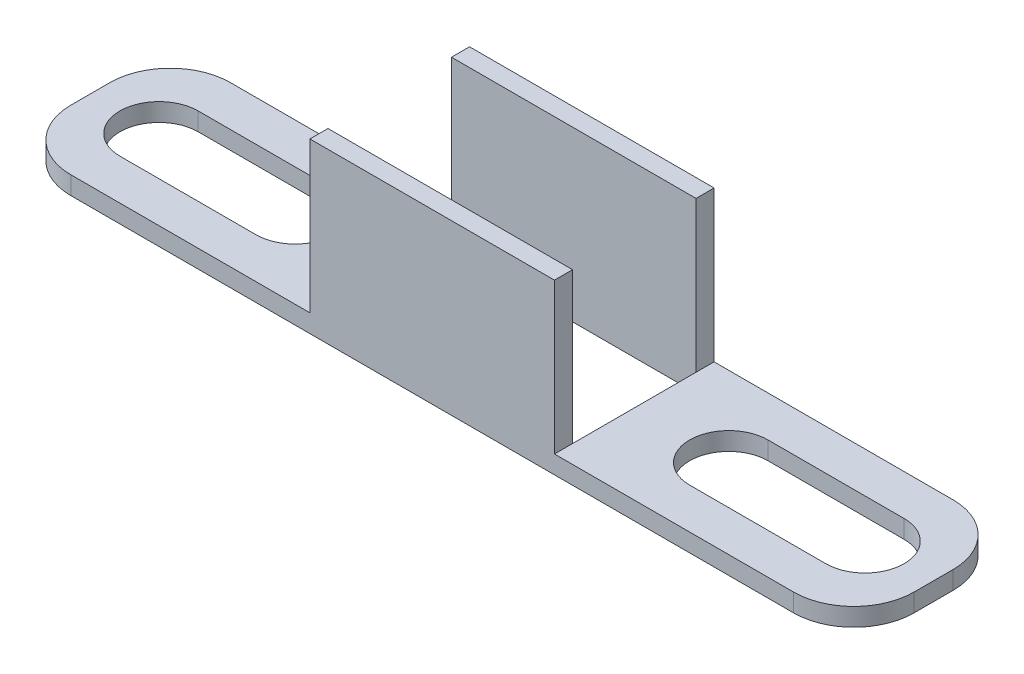
SolidWorks part; units mm, degrees
ref_plane "Front Plane" through (0, 0, 0) normal (0, 0, 1) x (1, 0, 0)
ref_plane "Top Plane" through (0, 0, 0) normal (0, 1, 0) x (1, 0, 0)
ref_plane "Right Plane" through (0, 0, 0) normal (1, 0, 0) x (0, 0, -1)
sketch "Sketch1" plane through (0, 0, 0) normal (0, 1, 0) x (1, 0, 0)
  line L0 (36, 0) -> (58.6, 0) construction
  line L1 (-20.3, -10.25) -> (20.3, -10.25)
  line L2 (-20.3, -10.25) -> (-20.3, 10.25)
  line L3 (-20.3, 10.25) -> (20.3, 10.25)
  line L4 (20.3, -10.25) -> (20.3, 10.25)
  line L5 (-20.3, -10.25) -> (20.3, 10.25) construction
  line L6 (-20.3, 10.25) -> (20.3, -10.25) construction
  line L7 (-70, -13.25) -> (70, -13.25)
  line L8 (-70, -13.25) -> (-70, 13.25)
  line L9 (-70, 13.25) -> (70, 13.25)
  line L10 (70, -13.25) -> (70, 13.25)
  line L11 (-70, -13.25) -> (70, 13.25) construction
  line L12 (-70, 13.25) -> (70, -13.25) construction
  line L13 (36, 6.5) -> (58.6, 6.5)
  line L14 (36, -6.5) -> (58.6, -6.5)
  line L15 (-36, 0) -> (-58.6, 0) construction
  line L16 (-36, -6.5) -> (-58.6, -6.5)
  line L17 (-36, 6.5) -> (-58.6, 6.5)
  arc A0 (36, 6.5) -> (36, -6.5) centre (36, 0) ccw
  arc A1 (58.6, -6.5) -> (58.6, 6.5) centre (58.6, 0) ccw
  arc A2 (-36, -6.5) -> (-36, 6.5) centre (-36, 0) ccw
  arc A3 (-58.6, 6.5) -> (-58.6, -6.5) centre (-58.6, 0) ccw
  point P0 (0, 0)
  point P6 (0, 0)
  point P13 (47.3, 0)
  point P18 (-47.3, 0)
  dimension "D6" = 22.6
  dimension "D9" = 72
  dimension "D10" = 36
  dimension "D1" = 40.6
  dimension "D2" = 20.5
  dimension "D3" = 140
  dimension "D4" = 26.5
  dimension "D5" = 13
  dimension "D7" = 22.6
  dimension "D8" = 13
extrude "Boss-Extrude1" add sketch "Sketch1" along normal blind 3
sketch "Sketch2" plane through (0, 3, 0) normal (0, 1, 0) x (1, 0, 0)
  line L0 (-70, -13.25) -> (70, -13.25) construction
  line L1 (-20.3, -10.25) -> (20.3, -10.25)
  line L2 (-20.3, -10.25) -> (-20.3, -13.25)
  line L3 (-20.3, -13.25) -> (20.3, -13.25)
  line L4 (20.3, -10.25) -> (20.3, -13.25)
  line L5 (70, 13.25) -> (-70, 13.25) construction
  line L6 (-20.3, 10.25) -> (20.3, 10.25)
  line L7 (-20.3, 10.25) -> (-20.3, 13.25)
  line L8 (-20.3, 13.25) -> (20.3, 13.25)
  line L9 (20.3, 10.25) -> (20.3, 13.25)
  dimension "D1" = 40.6
  dimension "D2" = 40.6
extrude "Boss-Extrude2" add sketch "Sketch2" along normal blind 25
fillet "Fillet1" radius 10 4 edges at (70, 1.5, -13.25) (70, 1.5, 13.25) (-70, 1.5, -13.25) (-70, 1.5, 13.25)
